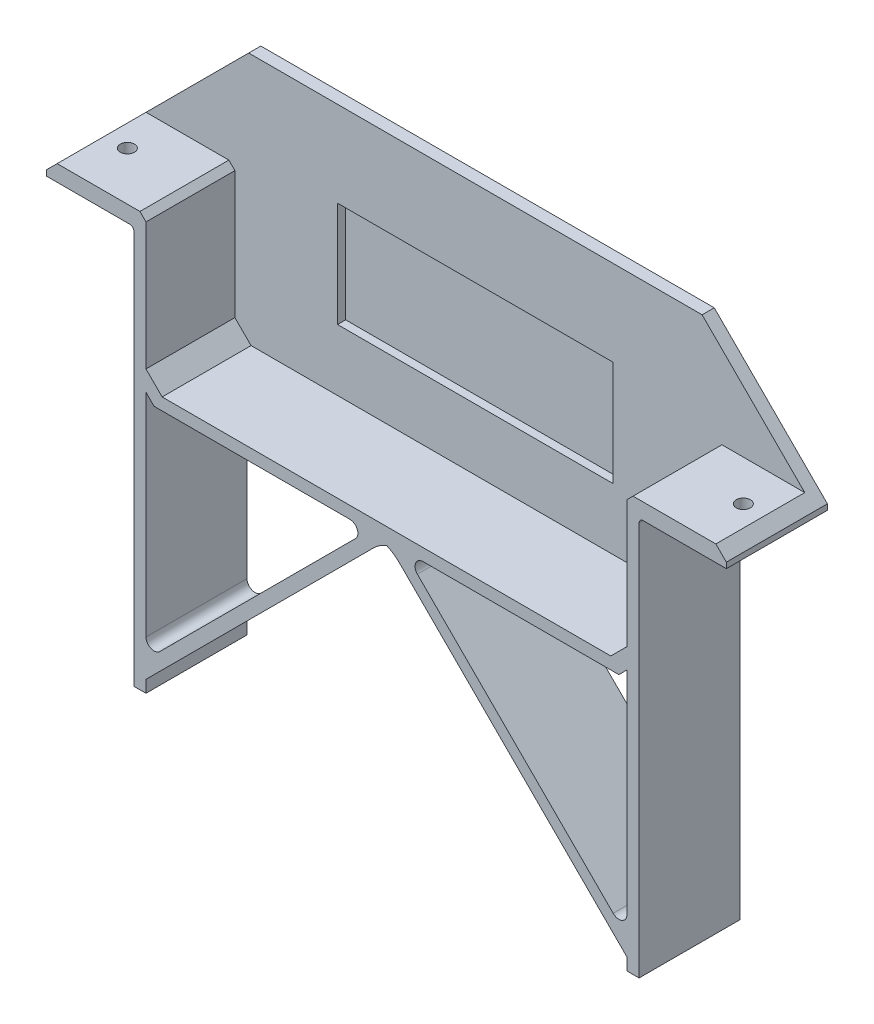
SolidWorks part; units mm, degrees
ref_plane "Front Plane" through (0, 0, 0) normal (0, 0, 1) x (1, 0, 0)
ref_plane "Top Plane" through (0, 0, 0) normal (0, 1, 0) x (1, 0, 0)
ref_plane "Right Plane" through (0, 0, 0) normal (1, 0, 0) x (0, 0, -1)
sketch "Sketch1" plane through (0, 0, 0) normal (0, 0, 1) x (1, 0, 0)
  line L1 (-62.5, -20) -> (62.5, -20)
  line L2 (-62.5, -20) -> (-62.5, 20)
  line L3 (-62.5, 20) -> (62.5, 20)
  line L4 (62.5, -20) -> (62.5, 20)
  line L5 (-62.5, -20) -> (62.5, 20) construction
  line L6 (-62.5, 20) -> (62.5, -20) construction
  point P0 (0, 0)
  dimension "D1" = 125
  dimension "D2" = 40
extrude "Boss-Extrude1" add sketch "Sketch1" along normal blind 3
sketch "Sketch2" plane through (0, 0, 3) normal (0, 0, 1) x (1, 0, 0)
  line L0 (-62.5, -20) -> (62.5, -20) construction
  line L1 (-62.5, 20) -> (-59.5, 20)
  line L2 (-62.5, 20) -> (-62.5, -20)
  line L3 (-62.5, -20) -> (-59.5, -20)
  line L4 (-59.5, 20) -> (-59.5, -20)
  line L6 (62.5, 20) -> (59.5, 20)
  line L7 (62.5, 20) -> (62.5, -20)
  line L8 (62.5, -20) -> (59.5, -20)
  line L9 (59.5, 20) -> (59.5, -20)
  dimension "D1" = 3
  dimension "D2" = 3
extrude "Boss-Extrude2" add sketch "Sketch2" along normal blind 22
sketch "Sketch4" plane through (-62.5, 0, 0) normal (-1, 0, 0) x (0, 0, 1)
  line L0 (25, 20) -> (25, -20) construction
  line L1 (0, 20) -> (25, 20)
  line L2 (0, 20) -> (0, 16)
  line L3 (0, 16) -> (25, 16)
  line L4 (25, 20) -> (25, 16)
  dimension "D1" = 4
extrude "Boss-Extrude4" add sketch "Sketch4" along normal blind 21.59
sketch "Sketch5" plane through (62.5, 0, 0) normal (1, 0, 0) x (0, 0, -1)
  line L0 (-25, -20) -> (-25, 20) construction
  line L1 (0, 20) -> (-25, 20)
  line L2 (0, 20) -> (0, 16)
  line L3 (0, 16) -> (-25, 16)
  line L4 (-25, 20) -> (-25, 16)
  dimension "D1" = 4
extrude "Boss-Extrude5" add sketch "Sketch5" along normal blind 21.59
sketch "Sketch6" plane through (0, 0, 0) normal (0, 0, -1) x (-1, 0, 0)
  line L1 (-84.09, 20) -> (84.09, 20)
  line L2 (-84.09, 20) -> (-84.09, 45.4)
  line L3 (-84.09, 45.4) -> (84.09, 45.4)
  line L4 (84.09, 20) -> (84.09, 45.4)
  dimension "D1" = 25.4
extrude "Boss-Extrude6" add sketch "Sketch6" against normal blind 3
chamfer "Chamfer1" distance 28 angle 45 2 edges at (-84.09, 45.4, 1.5) (84.09, 45.4, 1.5)
sketch "Sketch7" plane through (0, 0, 3) normal (0, 0, 1) x (1, 0, 0)
  line L1 (-59.5, -20) -> (-59.5, 20) construction
  line L6 (-34.1, 24.2172) -> (34.1, 24.2172)
  line L7 (-34.1, 24.2172) -> (-34.1, -1.7828)
  line L8 (-34.1, -1.7828) -> (34.1, -1.7828)
  line L9 (34.1, 24.2172) -> (34.1, -1.7828)
  line L10 (59.5, 20) -> (59.5, -20) construction
  dimension "D1" = 26
  dimension "D4" = 25.4
  dimension "D5" = 25.4
extrude "Cut-Extrude1" cut sketch "Sketch7" against normal blind 2
sketch "Sketch9" plane through (0, 0, 3) normal (0, 0, 1) x (1, 0, 0)
  line L0 (59.5, 20) -> (59.5, -20) construction
  line L1 (-59.5, -20) -> (59.5, -20)
  line L2 (-59.5, -20) -> (-59.5, -17)
  line L3 (-59.5, -17) -> (59.5, -17)
  line L4 (59.5, -20) -> (59.5, -17)
  dimension "D1" = 3
extrude "Boss-Extrude7" add sketch "Sketch9" along normal blind 22
chamfer "Chamfer2" distance 4 angle 45 2 edges at (-59.5, -17, 14) (59.5, -17, 14)
chamfer "Chamfer3" distance 5 angle 45 2 edges at (-62.5, -20, 12.5) (62.5, -20, 12.5)
sketch "Sketch11" plane through (0, 20, 0) normal (0, 1, 0) x (1, 0, 0)
  line L0 (-84.09, 0) -> (-56.09, 0) construction
  line L1 (56.09, 0) -> (84.09, 0) construction
  line L2 (-84.09, -25) -> (-84.09, 0) construction
  circle A0 centre (-76.11, -13) radius 1.75
  circle A1 centre (76.29, -13) radius 1.75
  dimension "D1" = 3.5
  dimension "D2" = 3.5
  dimension "D3" = 13
  dimension "D4" = 13
  dimension "D5" = 152.4
  dimension "D6" = 7.98
extrude "Cut-Extrude3" cut sketch "Sketch11" against normal blind 5
fillet "Fillet1" radius 1 2 edges at (62.5, 16, 12.5) (-62.5, 16, 12.5)
chamfer "Chamfer4" distance 1.5 angle 45 2 edges at (-59.5, 20, 14) (59.5, 20, 14)
sketch "Sketch12" plane through (0, 0, 25) normal (0, 0, 1) x (1, 0, 0)
  line L0 (-0.2758, -20.2758) -> (-59.5, -79.5)
  line L1 (-57.5, -20) -> (57.5, -20) construction
  line L2 (0.2758, -20.2758) -> (59.5, -79.5)
  line L3 (59.5, -79.5) -> (59.5, -82.5)
  line L4 (59.5, -75.2574) -> (4.2426, -20)
  line L5 (4.2426, -20) -> (0, -20)
  line L6 (-59.5, -79.5) -> (-59.5, -82.5)
  line L7 (-59.5, -75.2574) -> (-4.2426, -20)
  line L8 (-4.2426, -20) -> (0, -20)
  line L9 (-0.2758, -20.2758) -> (0.2758, -20.2758)
  line L10 (-62.5, -15) -> (-59.5, -15)
  line L11 (-62.5, -15) -> (-62.5, -82.5)
  line L12 (-62.5, -82.5) -> (-59.5, -82.5)
  line L13 (-59.5, -15) -> (-59.5, -75.2574)
  line L14 (62.5, -15) -> (59.5, -15)
  line L15 (62.5, -15) -> (62.5, -82.5)
  line L16 (62.5, -82.5) -> (59.5, -82.5)
  line L17 (59.5, -15) -> (59.5, -75.2574)
  dimension "D3" = 3
  dimension "D4" = 3
extrude "Boss-Extrude10" add sketch "Sketch12" against normal blind 25
fillet "Fillet2" radius 10 2 edges at (0.2758, -20.2758, 12.5) (-0.2758, -20.2758, 12.5)
fillet "Fillet3" radius 2 2 edges at (59.5, -75.2574, 12.5) (-59.5, -75.2574, 12.5)
fillet "Fillet4" radius 2 2 edges at (4.2426, -20, 12.5) (-4.2426, -20, 12.5)
